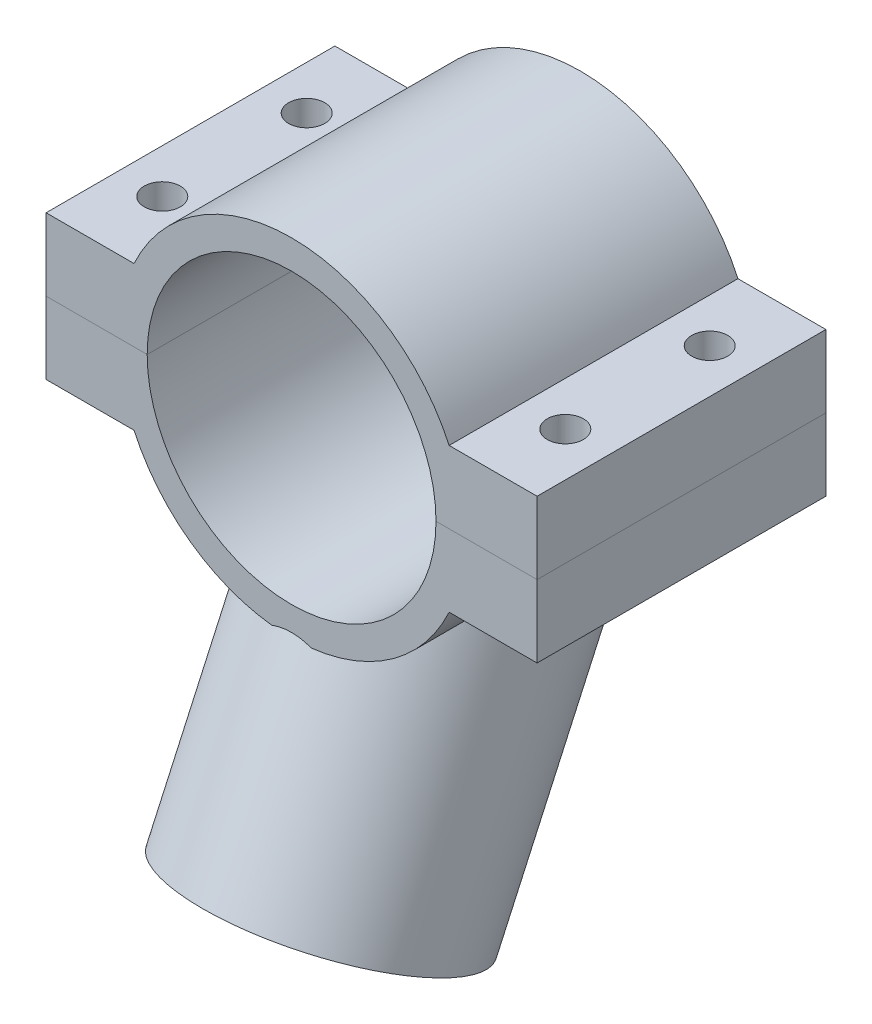
SolidWorks part; units mm, degrees
ref_plane "Front Plane" through (0, 0, 0) normal (0, 0, 1) x (1, 0, 0)
ref_plane "Top Plane" through (0, 0, 0) normal (0, 1, 0) x (1, 0, 0)
ref_plane "Right Plane" through (0, 0, 0) normal (1, 0, 0) x (0, 0, -1)
sketch "Sketch1" plane through (0, 0, 0) normal (0, 0, 1) x (1, 0, 0)
  circle A0 centre (0, 0) radius 20
  circle A1 centre (0, 0) radius 24
  dimension "D1" = 40
  dimension "D2" = 4
extrude "Boss-Extrude1" add sketch "Sketch1" along normal blind 40
sketch "Sketch2" plane through (0, 0, 0) normal (0, 1, 0) x (1, 0, 0)
  line L0 (-20, 0) -> (-34, 0)
  line L1 (-34, 0) -> (-34, -40)
  line L2 (-34, -40) -> (-20, -40)
  line L4 (20, 0) -> (34, 0)
  line L5 (34, 0) -> (34, -40)
  line L6 (34, -40) -> (20, -40)
  line L8 (-20, 0) -> (-20, -40)
  line L9 (20, -40) -> (20, 0)
  dimension "D1" = 14
extrude "Boss-Extrude2" add sketch "Sketch2" along normal blind 10 and the other way blind 10
ref_plane "Plane1" through (0, -20, 0) normal (0, 1, 0) x (1, 0, 0)
sketch "Sketch5" plane through (0, 10, 0) normal (0, 1, 0) x (1, 0, 0)
  line L0 (-27.9087, 0) -> (-27.9087, -40) construction
  line L1 (-21.8174, 0) -> (-34, 0) construction
  line L2 (-34, -40) -> (-21.8174, -40) construction
  circle A0 centre (-27.9087, -10) radius 2.5
  circle A1 centre (-27.9087, -30) radius 2.5
  point P10 (-27.9087, -6.217)
  point P11 (-27.9087, -31.3147)
  point P12 (-27.9087, -6.7686)
  point P13 (-27.9087, -6.5848)
  point P14 (0, 0)
  point P16 (0, 0)
  dimension "D1" = 5
  dimension "D2" = 10
  dimension "D3" = 10
extrude "Cut-Extrude1" cut sketch "Sketch5" against normal up to next
mirror "Mirror1" about plane through (0, 0, 0) normal (1, 0, 0) of "Cut-Extrude1"
split "Split1" trim tools "Top Plane" bodies to split 105 resulting bodies 106 107
ref_plane "Plane2" through (0, -6.8139, 3.1053) normal (0, -0.91, 0.4147) x (1, 0, 0)
ref_plane "Plane3" through (0, -34.1127, 15.5461) normal (0, -0.91, 0.4147) x (1, 0, 0)
sketch "Sketch6" plane through (0, -34.1127, 15.5461) normal (0, -0.91, 0.4147) x (1, 0, 0)
  line L0 (-21.8174, 8.721) -> (21.8174, 8.721) construction
  line L3 (21.8174, -4.1469) -> (21.8174, 32.2515) construction
  line L4 (-21.8174, -4.1469) -> (-21.8174, 32.2515) construction
  circle A0 centre (0, 8.721) radius 18
  point P2 (0, 0)
  point P5 (0, 0)
  dimension "D1" = 36
extrude "Boss-Extrude4" add sketch "Sketch6" along normal blind 30 and the other way up to next
